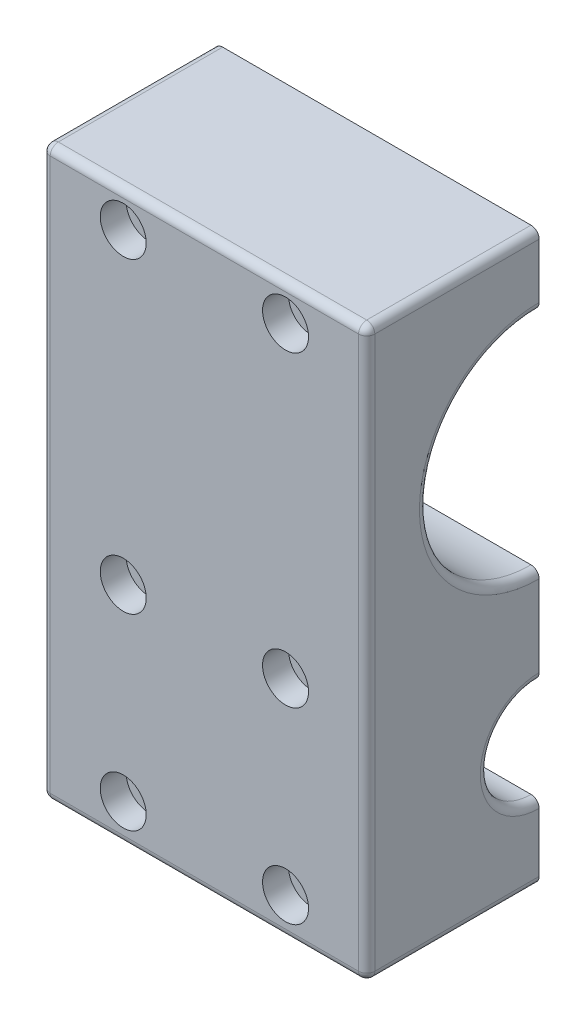
SolidWorks part; units mm, degrees
note: The reader was unsure of these and kept them because the rebuilt part matched: shared geometry of "Sketch5<3>".
ref_plane "Front Plane" through (0, 0, 0) normal (0, 0, 1) x (1, 0, 0)
ref_plane "Top Plane" through (0, 0, 0) normal (0, 1, 0) x (1, 0, 0)
ref_plane "Right Plane" through (0, 0, 0) normal (1, 0, 0) x (0, 0, -1)
sketch "Sketch1" plane through (0, 0, 0) normal (1, 0, 0) x (0, 0, -1)
  line L1 (0, 0) -> (53.975, 0)
  line L2 (0, 0) -> (0, 88.9)
  line L3 (0, 88.9) -> (53.975, 88.9)
  line L4 (53.975, 0) -> (53.975, 88.9)
  circle A0 centre (26.9875, 19.685) radius 7.9375
  circle A1 centre (26.9875, 60.325) radius 17.4625
  point P11 (26.9875, 88.9)
  dimension "D1" = 15.875
  dimension "D2" = 34.925
  dimension "D5" = 40.64
  dimension "D3" = 53.975
  dimension "D4" = 88.9
  dimension "D6" = 28.575
extrude "Boss-Extrude1" add sketch "Sketch1" along normal blind 50.8 contours A1 | A0 | L4 L3 L2 L1
sketch "Sketch5" plane through (0, 0, 0) normal (0, 0, 1) x (1, 0, 0)
  circle A0 centre (38.1, 35.2425) radius 2.09
  circle A1 centre (38.1, 35.2425) radius 3.6
  circle A2 centre (12.7, 83.3438) radius 2.09
  circle A3 centre (12.7, 83.3438) radius 3.6
  circle A4 centre (38.1, 83.3438) radius 2.09
  circle A5 centre (38.1, 83.3438) radius 3.6
  circle A6 centre (12.7, 35.2425) radius 2.09
  circle A7 centre (12.7, 35.2425) radius 3.6
  circle A8 centre (38.1, 5.8737) radius 2.09
  circle A9 centre (38.1, 5.8737) radius 3.6
  circle A10 centre (12.7, 5.8737) radius 2.09
  circle A11 centre (12.7, 5.8737) radius 3.6
  dimension "D3" = 4.18
  dimension "D4" = 4.18
  dimension "D5" = 4.18
  dimension "D6" = 4.18
  dimension "D7" = 4.18
  dimension "D8" = 4.18
  dimension "D9" = 7.2
  dimension "D10" = 7.2
  dimension "D11" = 7.2
  dimension "D12" = 7.2
  dimension "D13" = 7.2
  dimension "D14" = 7.2
  dimension "D1" = 25.4
  dimension "D2" = 12.7
extrude "Cut-Extrude1" cut sketch "Sketch5" against normal through all contours A2 | A6 | A4 | A0 | A10 | A8
extrude "Cut-Extrude2" cut sketch "Sketch5<3>" against normal blind 4.064 contours A3 | A5 | A1 | A7 | A11 | A9
sketch "Sketch5<3>" plane through (0, 0, 0) normal (0, 0, 1) x (1, 0, 0) same geometry as "Sketch5"
sketch "Sketch6" plane through (0, 0, -53.975) normal (0, 0, -1) x (-1, 0, 0)
  line L109 (-34.0286, 83.3438) -> (-36.0643, 86.8697)
  line L110 (-36.0643, 86.8697) -> (-40.1357, 86.8697)
  line L111 (-40.1357, 86.8697) -> (-42.1715, 83.3438)
  line L112 (-42.1715, 83.3438) -> (-40.1357, 79.8178)
  line L113 (-40.1357, 79.8178) -> (-36.0643, 79.8178)
  line L114 (-36.0643, 79.8178) -> (-34.0286, 83.3438)
  line L115 (-8.6286, 83.3438) -> (-10.6643, 86.8697)
  line L116 (-10.6643, 86.8697) -> (-14.7357, 86.8697)
  line L117 (-14.7357, 86.8697) -> (-16.7714, 83.3438)
  line L118 (-16.7714, 83.3438) -> (-14.7357, 79.8178)
  line L119 (-14.7357, 79.8178) -> (-10.6643, 79.8178)
  line L120 (-10.6643, 79.8178) -> (-8.6286, 83.3438)
  line L121 (-8.6286, 35.2425) -> (-10.6643, 38.7685)
  line L122 (-10.6643, 38.7685) -> (-14.7357, 38.7685)
  line L123 (-14.7357, 38.7685) -> (-16.7714, 35.2425)
  line L124 (-16.7714, 35.2425) -> (-14.7357, 31.7165)
  line L125 (-14.7357, 31.7165) -> (-10.6643, 31.7165)
  line L126 (-10.6643, 31.7165) -> (-8.6286, 35.2425)
  line L127 (-34.0286, 35.2425) -> (-36.0643, 38.7685)
  line L128 (-36.0643, 38.7685) -> (-40.1357, 38.7685)
  line L129 (-40.1357, 38.7685) -> (-42.1714, 35.2425)
  line L130 (-42.1714, 35.2425) -> (-40.1357, 31.7165)
  line L131 (-40.1357, 31.7165) -> (-36.0643, 31.7165)
  line L132 (-36.0643, 31.7165) -> (-34.0286, 35.2425)
  line L133 (-34.0286, 5.8737) -> (-36.0643, 9.3997)
  line L134 (-36.0643, 9.3997) -> (-40.1357, 9.3997)
  line L135 (-40.1357, 9.3997) -> (-42.1715, 5.8737)
  line L136 (-42.1715, 5.8737) -> (-40.1357, 2.3478)
  line L137 (-40.1357, 2.3478) -> (-36.0643, 2.3478)
  line L138 (-36.0643, 2.3478) -> (-34.0286, 5.8737)
  line L139 (-8.6286, 5.8737) -> (-10.6643, 9.3997)
  line L140 (-10.6643, 9.3997) -> (-14.7357, 9.3997)
  line L141 (-14.7357, 9.3997) -> (-16.7715, 5.8737)
  line L142 (-16.7715, 5.8737) -> (-14.7357, 2.3478)
  line L143 (-14.7357, 2.3478) -> (-10.6643, 2.3478)
  line L144 (-10.6643, 2.3478) -> (-8.6286, 5.8737)
  circle A0 centre (-38.1, 83.3438) radius 4.0714 construction
  circle A1 centre (-12.7, 83.3438) radius 4.0714 construction
  circle A2 centre (-12.7, 35.2425) radius 4.0714 construction
  circle A3 centre (-38.1, 35.2425) radius 4.0714 construction
  circle A4 centre (-38.1, 5.8737) radius 4.0714 construction
  circle A5 centre (-12.7, 5.8737) radius 4.0714 construction
  circle M1 centre (-12.7, 5.8737) radius 2.09
  circle M2 centre (-38.1, 35.2425) radius 2.09
  circle M3 centre (-38.1, 83.3438) radius 2.09
  circle M4 centre (-12.7, 35.2425) radius 2.09
  circle M5 centre (-38.1, 5.8737) radius 2.09
  dimension "D1" = 8.1429
  dimension "D2" = 8.1429
  dimension "D3" = 8.1429
  dimension "D4" = 8.1429
  dimension "D5" = 8.1429
  dimension "D6" = 8.1429
extrude "Cut-Extrude3" cut sketch "Sketch6" against normal blind 2.54 contours L119 L120 L115 L116 L117 L118 M3 | L125 L126 L121 L122 L123 L124 M2 | L131 L132 L127 L128 L129 L130 M4 | L143 L144 L139 L140 L141 L142 M5 | L137 L138 L133 L134 L135 L136 M1
fillet "Fillet1" radius 1.27 16 edges at (25.4, 0, 0) (25.4, 0, -53.975) (0, 19.685, -34.925) (0, 0, -26.9875) (50.8, 19.685, -34.925) (50.8, 0, -26.9875) (50.8, 60.325, -44.45) (50.8, 44.45, 0) (50.8, 44.45, -53.975) (0, 60.325, -44.45) (0, 44.45, 0) (0, 44.45, -53.975) (25.4, 88.9, 0) (0, 88.9, -26.9875) (50.8, 88.9, -26.9875) (25.4, 88.9, -53.975)
ref_plane "Plane1" through (0, 0, -26.9875) normal (0, 0, 1) x (1, 0, 0)
other "SurfaceCut1"
ref_plane "Plane2" through (0, 11, 0) normal (0, 1, 0) x (1, 0, 0)
other "SurfaceCut2"
